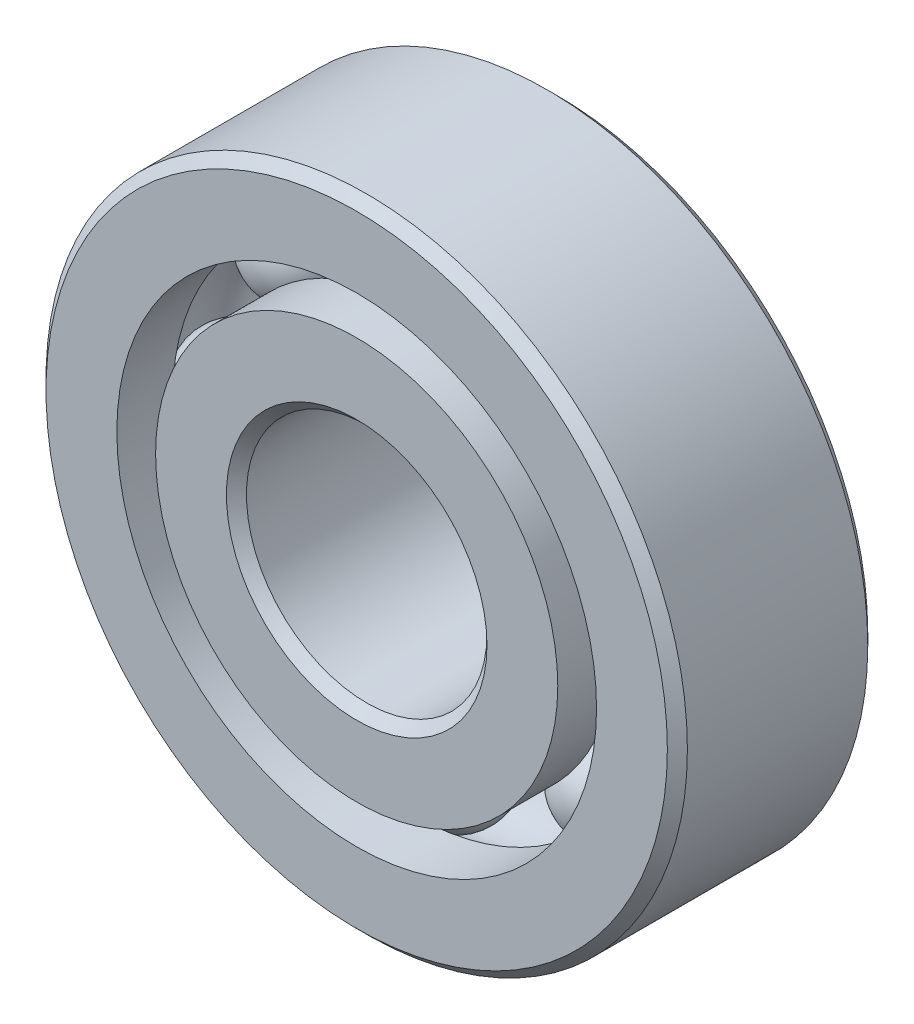
SolidWorks part; units mm, degrees
ref_plane "Front Plane" through (0, 0, 0) normal (0, 0, 1) x (1, 0, 0)
ref_plane "Top Plane" through (0, 0, 0) normal (0, 1, 0) x (1, 0, 0)
ref_plane "Right Plane" through (0, 0, 0) normal (1, 0, 0) x (0, 0, -1)
sketch "Sketch1" plane through (0, 0, 0) normal (1, 0, 0) x (0, 0, -1)
  line L0 (-1.9844, 0) -> (1.9844, 0) construction
  line L1 (0, 6.35) -> (0, -6.35) construction
  line L2 (1.7859, 6.35) -> (-1.7859, 6.35)
  line L3 (-1.7859, 6.35) -> (-1.9844, 6.1516)
  line L4 (-1.9844, 6.1516) -> (-1.9844, 4.7494)
  line L5 (-1.9844, 4.7494) -> (-0.8819, 4.7494)
  line L6 (1.9844, 4.7494) -> (0.8819, 4.7494)
  line L7 (1.9844, 6.1516) -> (1.9844, 4.7494)
  line L8 (1.7859, 6.35) -> (1.9844, 6.1516)
  line L9 (0, 6.35) -> (0, 4.3656) construction
  line L10 (0, 4.3656) -> (0, 2.3813) construction
  arc A0 (-0.8819, 4.7494) -> (0.8819, 4.7494) centre (0, 4.3656) cw
  point P14 (0, 2.3813)
  dimension "Width" = 3.9688
  dimension "OD" = 12.7
  dimension "D1" = 45
  dimension "D2" = 0.1984
  dimension "Shaft Dia" = 4.7625
  dimension "D3" = 1.7639
  dimension "D4" = 0.3838
revolve "Revolve1" add sketch "Sketch1" angle 360 about L0
sketch "Sketch3" plane through (0, 0, 0) normal (1, 0, 0) x (0, 0, -1)
  line L0 (-1.9844, 3.9818) -> (-0.8819, 3.9818)
  line L1 (0, 6.35) -> (0, -6.35) construction
  line L2 (-1.9844, 6.1516) -> (-1.9844, 4.7494) construction
  line L3 (-1.9844, 3.9818) -> (-1.9844, 2.5797)
  line L4 (-1.7859, 6.35) -> (-1.9844, 6.1516) construction
  line L5 (-1.9844, 2.5797) -> (-1.7859, 2.3813)
  line L6 (-1.7859, 2.3813) -> (1.7859, 2.3813)
  line L7 (1.7859, 6.35) -> (1.7859, -6.35) construction
  line L8 (1.7859, 2.3813) -> (1.9844, 2.5797)
  line L9 (1.9844, -6.1516) -> (1.9844, 6.1516) construction
  line L10 (1.9844, 2.5797) -> (1.9844, 3.9818)
  line L11 (1.9844, 3.9818) -> (0.8819, 3.9818)
  line L13 (1.7859, 6.35) -> (1.9844, 6.1516) construction
  arc A0 (0.8819, 4.7494) -> (-0.8819, 4.7494) centre (0, 4.3656) ccw construction
  arc A1 (0.8819, 3.9818) -> (-0.8819, 3.9818) centre (0, 4.3656) cw
revolve "Revolve3" add sketch "Sketch3" angle 360 about L0
sketch "Sketch4" plane through (0, 0, 0) normal (1, 0, 0) x (0, 0, -1)
  line L0 (-0.9618, 4.3656) -> (0.9618, 4.3656)
  arc A2 (-0.9618, 4.3656) -> (0.9618, 4.3656) centre (0, 4.3656) cw
  arc A3 (0.8819, 4.7494) -> (-0.8819, 4.7494) centre (0, 4.3656) ccw construction
revolve "Revolve4" add sketch "Sketch4" angle 360 about L0
ref_axis "Axis1" through (0, 0, -1.9844) along (0, 0, 1)
pattern_circular "CirPattern1" count 8 every 45 about axis through (0, 0, -1.9844) along (0, 0, 1) of bodies 104
sketch "Sketch5" plane through (0, 0, 0) normal (1, 0, 0) x (0, 0, -1)
  line L0 (-1.9844, 4.7494) -> (-0.8819, 4.7494) construction
  line L1 (-1.8852, 4.7494) -> (-0.9618, 4.7494)
  line L2 (-1.8852, 4.7494) -> (-1.8852, 3.9818)
  line L3 (-1.8852, 3.9818) -> (-0.9618, 3.9818)
  line L4 (-0.9618, 4.7494) -> (-0.9618, 3.9818)
  line L5 (-1.9844, 3.9818) -> (-0.8819, 3.9818) construction
  line L6 (1.9844, 4.7494) -> (0.8819, 4.7494) construction
  line L7 (1.8852, 4.7494) -> (0.9618, 4.7494)
  line L8 (1.8852, 4.7494) -> (1.8852, 3.9818)
  line L9 (1.8852, 3.9818) -> (0.9618, 3.9818)
  line L10 (0.9618, 4.7494) -> (0.9618, 3.9818)
  line L11 (1.9844, 3.9818) -> (0.8819, 3.9818) construction
  line L12 (-1.7859, 6.35) -> (-1.9844, 6.1516) construction
  point P18 (-1.8852, 6.2508)
revolve "Revolve5" [suppressed] add sketch "Sketch5" angle 360 about L0
equation "\"D2@Sketch1\" = \"Width@Sketch1\"*.05"
equation "\"D3@Sketch1\" = \"Width@Sketch1\"/2.25"
equation "\"D4@Sketch1\" = (((\"OD@Sketch1\"-\"Width@Sketch1\")/2)/3.25)/3.5"
equation "\"D2@CirPattern1\" = 360/\"Balls@CirPattern1\""
